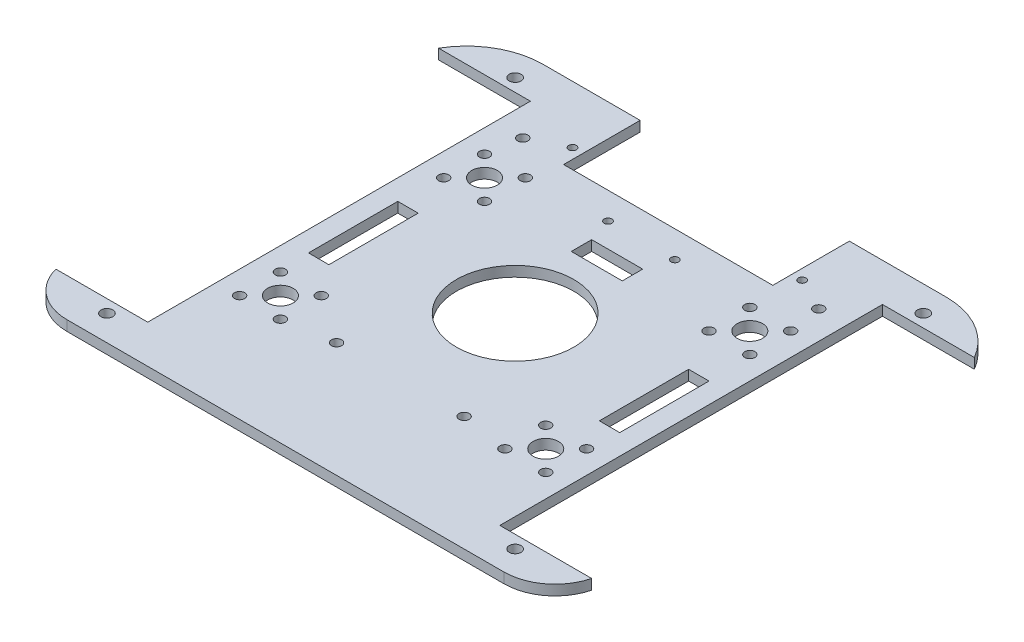
SolidWorks part; units mm, degrees
ref_plane "Front Plane" through (0, 0, 0) normal (0, 0, 1) x (1, 0, 0)
ref_plane "Top Plane" through (0, 0, 0) normal (0, 1, 0) x (1, 0, 0)
ref_plane "Right Plane" through (0, 0, 0) normal (1, 0, 0) x (0, 0, -1)
sketch "Sketch1" plane through (0, 0, 0) normal (0, 1, 0) x (1, 0, 0)
  line L0 (-153.1481, 75) -> (-117.1481, 75)
  line L2 (56.8519, 90) -> (56.8519, 75)
  line L3 (56.8519, -90) -> (-153.1481, -90)
  line L4 (-153.1481, 90) -> (-153.1481, 75)
  line L5 (-153.1481, 90) -> (-129.1481, 90)
  line L6 (-117.1481, 0) -> (-153.1481, 0) construction
  line L7 (-117.1481, 75) -> (-117.1481, -75)
  line L8 (-117.1481, -75) -> (-153.1481, -75)
  line L9 (-48.1481, 90) -> (-48.1481, -90) construction
  line L10 (20.8519, -75) -> (56.8519, -75)
  line L11 (20.8519, 75) -> (20.8519, -75)
  line L12 (56.8519, 75) -> (20.8519, 75)
  line L13 (-153.1481, -75) -> (-153.1481, -90)
  line L14 (56.8519, -75) -> (56.8519, -90)
  line L15 (-48.1481, -40) -> (-117.1481, -40) construction
  line L16 (-48.1481, 0) -> (-117.1481, 0) construction
  line L17 (-89.1481, 73) -> (-89.1481, 60)
  line L22 (-89.1481, 60) -> (-7.1481, 60)
  line L23 (-7.1481, 60) -> (-7.1481, 80)
  line L24 (20.8519, 90) -> (56.8519, 90)
  line L27 (-129.1481, 90) -> (-89.1481, 90)
  line L28 (-89.1481, 90) -> (-89.1481, 73)
  line L29 (-7.1481, 80) -> (-7.1481, 90)
  line L30 (-7.1481, 90) -> (20.8519, 90)
  line L32 (-109.1481, 15) -> (-101.1481, 15)
  line L33 (-109.1481, 15) -> (-109.1481, -20)
  line L34 (-109.1481, -20) -> (-101.1481, -20)
  line L35 (-101.1481, 15) -> (-101.1481, -20)
  line L36 (4.8519, 15) -> (12.8519, 15)
  line L37 (4.8519, 15) -> (4.8519, -20)
  line L38 (4.8519, -20) -> (12.8519, -20)
  line L39 (12.8519, 15) -> (12.8519, -20)
  line L40 (-58.1481, 40) -> (-38.1481, 40)
  line L41 (-58.1481, 40) -> (-58.1481, 32)
  line L42 (-58.1481, 32) -> (-38.1481, 32)
  line L43 (-38.1481, 40) -> (-38.1481, 32)
  circle A4 centre (-128.1481, -80) radius 2.32
  circle A5 centre (-128.1481, 80) radius 2.32
  circle A6 centre (31.8519, 80) radius 2.32
  circle A7 centre (31.8519, -80) radius 2.32
  circle A8 centre (-108.1481, -48) radius 2
  circle A9 centre (-92.1481, -48) radius 2
  circle A10 centre (-92.1481, -32) radius 2
  circle A11 centre (-108.1481, -32) radius 2
  circle A12 centre (-100.1481, -40) radius 5
  circle A13 centre (-92.1481, 48) radius 2
  circle A14 centre (-108.1481, 48) radius 2
  circle A15 centre (-92.1481, 32) radius 2
  circle A16 centre (-100.1481, 40) radius 5
  circle A17 centre (-108.1481, 32) radius 2
  circle A18 centre (-4.1481, -32) radius 2
  circle A19 centre (-4.1481, -48) radius 2
  circle A20 centre (3.8519, -40) radius 5
  circle A21 centre (11.8519, -48) radius 2
  circle A22 centre (11.8519, -32) radius 2
  circle A23 centre (-4.1481, 32) radius 2
  circle A24 centre (-4.1481, 48) radius 2
  circle A25 centre (11.8519, 32) radius 2
  circle A26 centre (11.8519, 48) radius 2
  circle A27 centre (3.8519, 40) radius 5
  circle A28 centre (-48.1481, 0) radius 23
  circle A29 centre (-93.1481, 67.5) radius 1.5
  circle A30 centre (-3.1481, 67.5) radius 1.5
  circle A31 centre (-61.2481, 49.5) radius 1.5
  circle A32 centre (-35.0481, 49.5) radius 1.5
  circle A33 centre (-73.1481, -45) radius 2
  circle A34 centre (-23.1481, -45) radius 2
  circle A35 centre (9.8519, 61) radius 2
  circle A36 centre (-106.1481, 61) radius 2
  point P0 (0, 0)
  point P20 (-153.1481, -82.5)
  point P107 (0, 0)
  dimension "D9" = 28
  dimension "D7" = 75
  dimension "D10" = 25
  dimension "D2" = 28
  dimension "D12" = 27
  dimension "D14" = 16
  dimension "D17" = 8
  dimension "D20" = 4
  dimension "D22" = 55.9
  dimension "D36" = 25
  dimension "D38" = 14
  dimension "D1" = 210
  dimension "D3" = 36
  dimension "D4" = 150
  dimension "D5" = 15
  dimension "D6" = 15
  dimension "D8" = 15
  dimension "D11" = 5
  dimension "D13" = 9
  dimension "D15" = 27
  dimension "D16" = 8
  dimension "D18" = 32
  dimension "D19" = 30
  dimension "D21" = 22.5
  dimension "D23" = 40.5
  dimension "D24" = 8
  dimension "D25" = 8
  dimension "D26" = 8
  dimension "D27" = 8
  dimension "D28" = 35
  dimension "D29" = 35
  dimension "D30" = 45
  dimension "D31" = 45
  dimension "D32" = 8
  dimension "D33" = 20
  dimension "D34" = 59
  dimension "D35" = 20
  dimension "D37" = 45
  dimension "D39" = 17
extrude "Boss-Extrude1" add sketch "Sketch1" along normal blind 4
fillet "Fillet1" radius 30 2 edges at (-153.1481, 2, -90) (56.8519, 2, -90)
fillet "Fillet2" radius 20 2 edges at (56.8519, 2, 90) (-153.1481, 2, 90)
